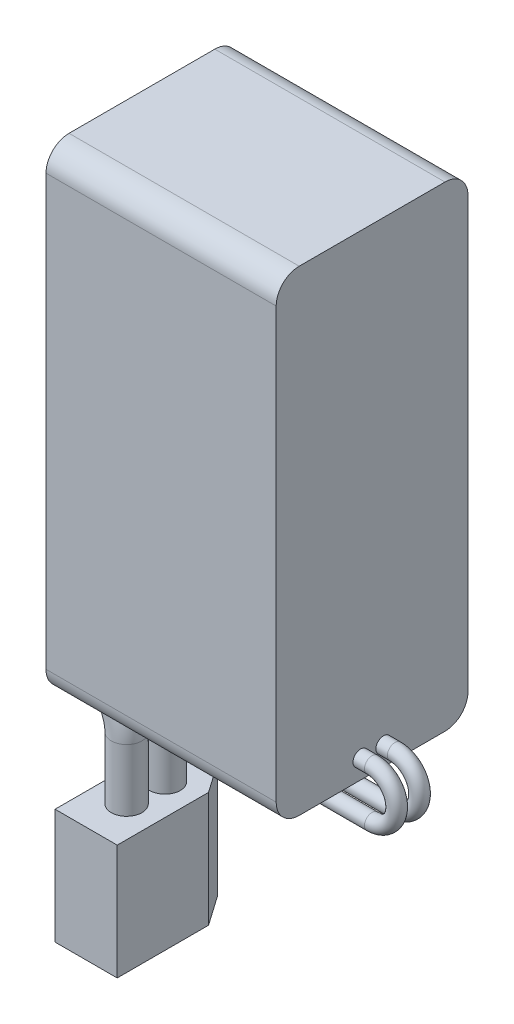
SolidWorks part; units mm, degrees
ref_plane "Front Plane" through (0, 0, 0) normal (1, 0, 0) x (0, 1, 0)
ref_plane "Top Plane" through (0, 0, 0) normal (0, 0, 1) x (0, 1, 0)
ref_plane "Right Plane" through (0, 0, 0) normal (0, 1, 0) x (-1, 0, 0)
sketch "Sketch1" plane through (0, 0, 0) normal (0, 0, 1) x (0, 1, 0)
  line L1 (-31, -15) -> (31, -15)
  line L2 (-31, -15) -> (-31, 15)
  line L3 (-31, 15) -> (31, 15)
  line L4 (31, -15) -> (31, 15)
  line L5 (-31, -15) -> (31, 15) construction
  line L6 (-31, 15) -> (31, -15) construction
  point P0 (0, 0)
  point P11 (0, 0)
  point P12 (0, 0)
  dimension "D1" = 62
  dimension "D2" = 30
extrude "Boss-Extrude1" add sketch "Sketch1" along normal blind 25
fillet "Fillet1" radius 3 4 edges at (0, -31, 0) (0, -31, 25) (0, 31, 0) (0, 31, 25)
sketch "Sketch2" plane through (-15, 0, 10) normal (1, 0, 0) x (0, 0, -1)
  line L0 (0, -28) -> (-5, -28) construction
  line L2 (-2.5, -28) -> (-2.5, -20.0823) construction
  line L3 (10, 28) -> (10, -28) construction
  line L4 (-15, 28) -> (-15, -28) construction
  line L5 (10, 28) -> (10, -28) construction
  line L6 (-15, 28) -> (-15, -28) construction
  line L7 (-12, -31) -> (7, -31) construction
  circle A0 centre (0, -28) radius 2
  circle A1 centre (-5, -28) radius 2
  point P13 (0, 0)
  point P14 (0, 0)
  dimension "D1" = 4
  dimension "D2" = 5
  dimension "D3" = 3
sketch "Sketch4" plane through (0, 0, 0) normal (0, 0, 1) x (0, 1, 0)
  line L0 (-28, 15) -> (-28, 17.6418)
  line L1 (-39.8327, 14.4947) -> (-47.9299, 14.4947)
  arc A0 (-28, 17.6418) -> (-33.9722, 18.6551) centre (-31.072, 17.6418) ccw
  arc A1 (-33.9722, 18.6551) -> (-39.8327, 14.4947) centre (-39.8327, 20.7027) cw
sweep "Sweep2" add profiles "Sketch2" path "Sketch4"
sketch "Sketch5" plane through (15, 0, 0) normal (1, 0, 0) x (0, 1, 0)
  line L0 (-28.5, 13.9916) -> (-28.5, 11.0084) construction
  line L1 (-28, 0) -> (28, 0) construction
  line L2 (-28, 25) -> (28, 25) construction
  line L3 (-28, 0) -> (28, 0) construction
  line L4 (-28, 25) -> (28, 25) construction
  line L5 (-28.5, 12.5) -> (-24.2481, 12.5) construction
  line L6 (-31, 22) -> (-31, 3) construction
  circle A0 centre (-28.5, 13.9916) radius 1
  circle A1 centre (-28.5, 11.0084) radius 1
  point P6 (0, 0)
  point P7 (0, 0)
  dimension "D1" = 2
  dimension "D2" = 2.5
sketch "Sketch6" plane through (0, 0, 0) normal (0, 0, 1) x (0, 1, 0)
  line L0 (-28.5, -16.4977) -> (-28.5, -15)
  line L1 (-34.9001, -16.4977) -> (-34.9001, 6.4232)
  arc A0 (-28.5, -16.4977) -> (-34.9001, -16.4977) centre (-31.7, -16.4977) cw
  point P0 (-28.5, -16.4977)
sweep "Sweep3" add profiles "Sketch5" path "Sketch6"
sketch "Sketch7" plane through (-6.4232, 0, 0) normal (-1, 0, 0) x (0, -1, 0)
  line L0 (34.9001, 12.5) -> (35.3785, 12.5) construction
  line L1 (33.4001, 9.5) -> (36.4001, 9.5)
  line L2 (33.4001, 9.5) -> (33.4001, 15.5)
  line L3 (33.4001, 15.5) -> (36.4001, 15.5)
  line L4 (36.4001, 9.5) -> (36.4001, 15.5)
  line L5 (33.4001, 9.5) -> (36.4001, 15.5) construction
  line L6 (33.4001, 15.5) -> (36.4001, 9.5) construction
  circle A0 centre (34.9001, 11.0084) radius 1 construction
  circle A1 centre (34.9001, 13.9916) radius 1 construction
  circle A2 centre (34.9001, 11.0084) radius 1 construction
  circle A3 centre (34.9001, 13.9916) radius 1 construction
  point P0 (34.9001, 12.5)
  dimension "D1" = 6
  dimension "D2" = 3
extrude "Boss-Extrude2" add sketch "Sketch7" along normal blind 3.5 draft 3
sketch "Sketch8" plane through (0, -47.9299, 0) normal (0, -1, 0) x (1, 0, 0)
  line L0 (-18.5447, 8.3691) -> (-15.8888, 4.576)
  line L1 (-15.8888, 4.576) -> (-13.1007, 4.576)
  line L2 (-18.5447, 8.3691) -> (-18.5447, 20.276)
  line L3 (-18.5447, 20.276) -> (-10.4447, 20.276)
  line L4 (-10.4447, 8.3691) -> (-10.4447, 20.276)
  line L5 (-18.5447, 4.576) -> (-10.4447, 20.276) construction
  line L6 (-18.5447, 20.276) -> (-10.4447, 4.576) construction
  line L7 (-13.1007, 4.576) -> (-10.4447, 8.3691)
  circle A0 centre (-14.4947, 10) radius 2 construction
  circle A1 centre (-14.4947, 15) radius 2 construction
  circle A2 centre (-14.4947, 10) radius 2 construction
  circle A3 centre (-14.4947, 15) radius 2 construction
  point P0 (-14.4947, 12.426)
  point P15 (-10.4447, 11.0013)
  point P16 (-18.5447, 10.1947)
  point P17 (0, 0)
  point P18 (0, 0)
  point P19 (-18.5447, 8.3691)
  dimension "D1" = 35
  dimension "D2" = 15.7
  dimension "D3" = 8.1
extrude "Boss-Extrude3" add sketch "Sketch8" along normal blind 15
